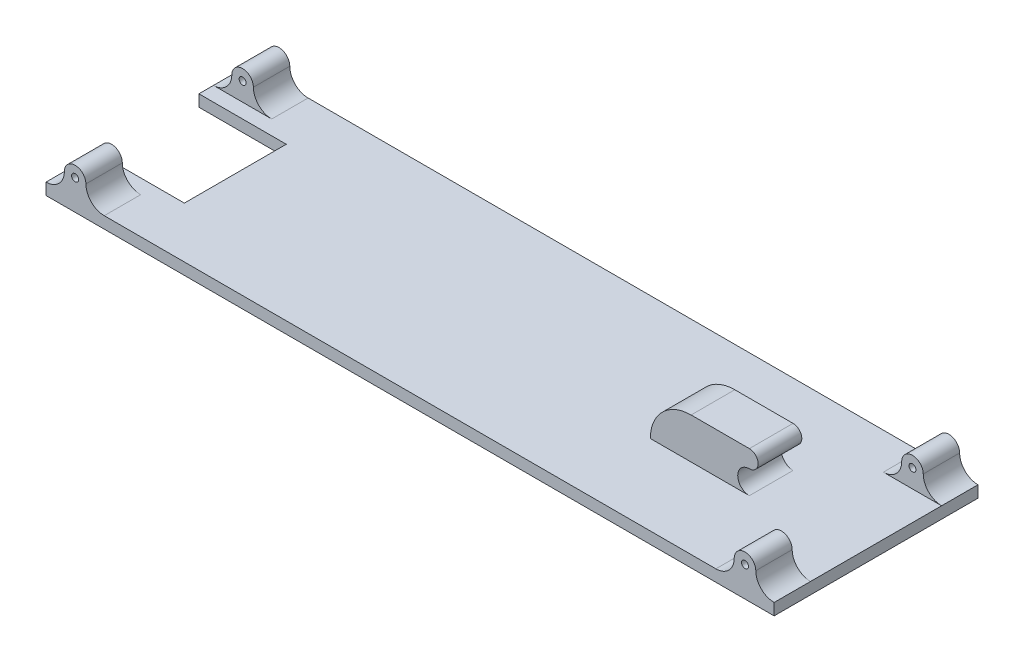
SolidWorks part; units mm, degrees
ref_plane "Front Plane" through (0, 0, 0) normal (0, 0, 1) x (1, 0, 0)
ref_plane "Top Plane" through (0, 0, 0) normal (0, 1, 0) x (1, 0, 0)
ref_plane "Right Plane" through (0, 0, 0) normal (1, 0, 0) x (0, 0, -1)
sketch "Sketch1" plane through (0, 0, 0) normal (0, 0, 1) x (1, 0, 0)
  line L1 (0, 0) -> (250, 0)
  line L2 (0, 0) -> (0, 4)
  line L3 (20, 4) -> (230, 4)
  line L4 (250, 0) -> (250, 4)
  circle A0 centre (10, 10.3) radius 1.2
  arc A1 (13.7, 10.3) -> (6.3, 10.3) centre (10, 10.3) ccw
  arc A2 (6.3, 10.3) -> (0, 4) centre (0, 10.3) cw
  arc A3 (13.7, 10.3) -> (20, 4) centre (20, 10.3) ccw
  circle A4 centre (240, 10.3) radius 1.2
  arc A5 (243.7, 10.3) -> (236.3, 10.3) centre (240, 10.3) ccw
  arc A6 (236.3, 10.3) -> (230, 4) centre (230, 10.3) cw
  arc A7 (243.7, 10.3) -> (250, 4) centre (250, 10.3) ccw
  point P13 (30, 5)
  point P20 (-8.8909, 16.0248)
  point P21 (0, 0)
  dimension "D3" = 2.4
  dimension "D4" = 2.5
  dimension "D5" = 20
  dimension "D1" = 4
  dimension "D2" = 250
extrude "Boss-Extrude1" add sketch "Sketch1" along normal mid plane 70
sketch "Sketch2" plane through (0, 0, 0) normal (1, 0, 0) x (0, 0, -1)
  line L0 (35, 14) -> (-35, 14) construction
  line L1 (22.5, 4) -> (-22.5, 4)
  line L2 (22.5, 4) -> (22.5, 14)
  line L3 (22.5, 14) -> (-22.5, 14)
  line L4 (-22.5, 4) -> (-22.5, 14)
  line L5 (22.5, 4) -> (-22.5, 14) construction
  line L6 (22.5, 14) -> (-22.5, 4) construction
  line L7 (-35, 4) -> (35, 4) construction
  point P0 (0, 9)
  point P9 (0, 0)
  dimension "D1" = 45
extrude "Cut-Extrude1" cut sketch "Sketch2" along normal through all
sketch "Sketch3" plane through (0, 0, 0) normal (0, 0, 1) x (1, 0, 0)
  line L0 (230, 4) -> (20, 4) construction
  line L1 (214, 18) -> (194, 18)
  line L2 (214, 4) -> (180, 4)
  arc A0 (214, 4) -> (214, 12) centre (214, 8) cw
  arc A1 (214, 12) -> (214, 18) centre (214, 15) ccw
  arc A2 (194, 18) -> (180, 4) centre (194, 4) ccw
  point P10 (0, 0)
  point P11 (0, 0)
  point P12 (178.2799, 4)
  point P14 (223.863, 11.9931)
  point P15 (222.5111, 16.5111)
  dimension "D1" = 3
  dimension "D2" = 4
  dimension "D3" = 20
  dimension "D4" = 180
extrude "Boss-Extrude2" add sketch "Sketch3" along normal mid plane 15
sketch "Sketch4" plane through (0, 4, 0) normal (0, 1, 0) x (1, 0, 0)
  line L0 (0, -22.5) -> (0, 22.5) construction
  line L1 (30, -17.5) -> (0, -17.5)
  line L2 (30, -17.5) -> (30, 17.5)
  line L3 (30, 17.5) -> (0, 17.5)
  line L4 (0, -17.5) -> (0, 17.5)
  line L5 (30, -17.5) -> (0, 17.5) construction
  line L6 (30, 17.5) -> (0, -17.5) construction
  point P0 (15, 0)
  point P7 (0, 0)
  point P8 (0, 0)
  dimension "D1" = 30
  dimension "D2" = 35
extrude "Cut-Extrude2" cut sketch "Sketch4" against normal through all
